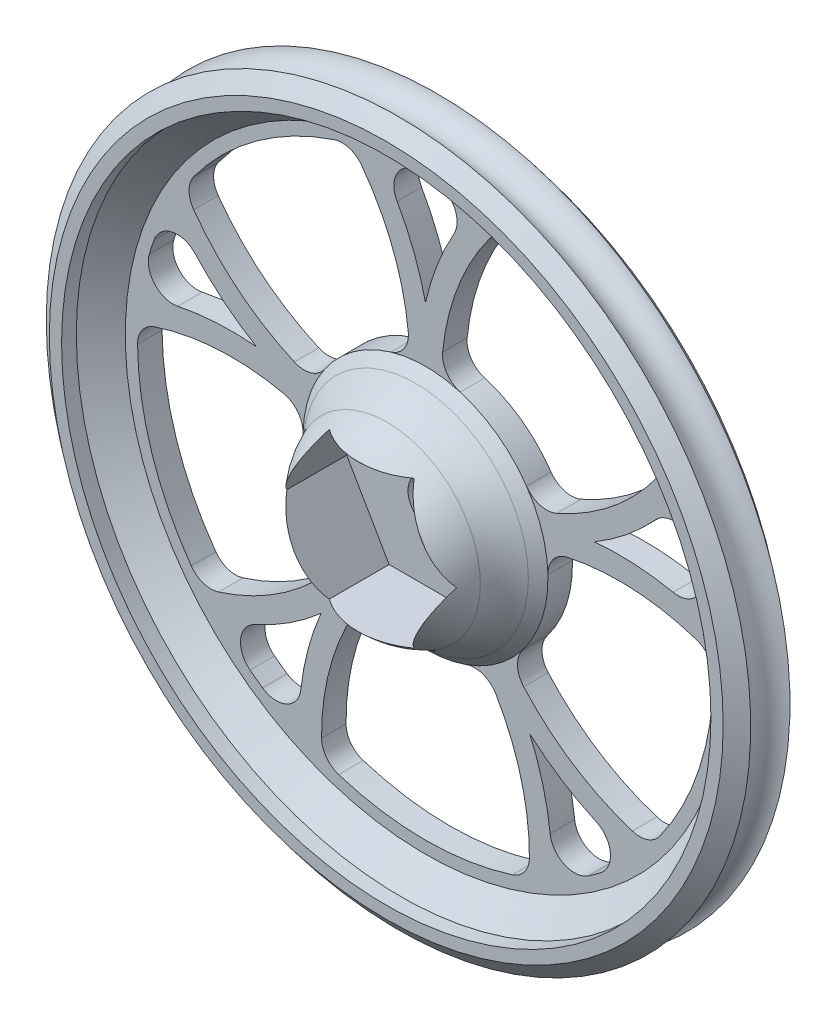
SolidWorks part; units mm, degrees
ref_plane "Front Plane" through (0, 0, 0) normal (0, 0, 1) x (1, 0, 0)
ref_plane "Top Plane" through (0, 0, 0) normal (0, 1, 0) x (1, 0, 0)
ref_plane "Right Plane" through (0, 0, 0) normal (1, 0, 0) x (0, 0, -1)
sketch "Sketch1" plane through (0, 0, 0) normal (1, 0, 0) x (0, 0, -1)
  line L0 (1, 1.925) -> (-1, 1.925)
  line L1 (-1, 8) -> (-1, 26.5)
  line L2 (-1, 26.5) -> (-4.2016, 26.5)
  line L3 (-4.2016, 26.5) -> (-4.2016, 27.5)
  line L4 (-4.2016, 27.5) -> (-3.2016, 28.75)
  line L5 (-3.2016, 28.75) -> (0, 28.75) construction
  line L6 (0, 28.75) -> (1, 27.5)
  line L7 (1, 27.5) -> (1, 26.5)
  line L8 (0, 1.925) -> (0, 26.5) construction
  line L9 (1, 26.5) -> (1, 1.925)
  line L10 (0, 0) -> (0, 1.925) construction
  line L11 (0, 0) -> (-35.662, 0) construction
  line L12 (-4.2016, 27.5) -> (1, 27.5) construction
  line L13 (-1, 26.5) -> (1, 26.5) construction
  line L14 (-1, 1.925) -> (-6.5, 1.925)
  line L15 (-6.5, 1.925) -> (-6.5, 8)
  line L16 (-6.5, 8) -> (-1, 8)
  arc A0 (-3.2016, 28.75) -> (0, 28.75) centre (-1.6008, 29.15) ccw
  dimension "D3" = 1.65
  dimension "D1" = 27.5
  dimension "D2" = 2
  dimension "D4" = 1
  dimension "D5" = 1
  dimension "D6" = 1.925
  dimension "D7" = 1.25
  dimension "D8" = 8
  dimension "D9" = 7.5
revolve "Revolve1" add sketch "Sketch1" angle 360 about L11
chamfer "Chamfer1" distance 2 angle 45 3 edges at (-8, 0, 6.5) (-8, 0, 1) (-26.5, 0, 1)
sketch "Sketch2" plane through (0, 0, 6.5) normal (0, 0, 1) x (1, 0, 0)
  line L0 (3.4641, 6) -> (-3.4641, 6)
  line L1 (-3.4641, 6) -> (-6.9282, 0)
  line L2 (-6.9282, 0) -> (-3.4641, -6)
  line L3 (-3.4641, -6) -> (3.4641, -6)
  line L4 (3.4641, -6) -> (6.9282, 0)
  line L5 (6.9282, 0) -> (3.4641, 6)
  circle A0 centre (0, 0) radius 6.9282 construction
  point P8 (4.4333, -1.0405)
  point P10 (0, 0)
  point P11 (0, 0)
  point P12 (0, 0)
  point P13 (1.925, -2.4583)
  point P14 (0, 0)
  point P15 (0, 0)
  dimension "D1" = 12
extrude "Cut-Extrude1" cut sketch "Sketch2" against normal blind 6
sketch "Sketch4" plane through (0, 0, 1) normal (0, 0, 1) x (1, 0, 0)
  line L0 (0, 0) -> (0, 24.5) construction
  line L1 (0, 0) -> (-23.3009, 7.5709) construction
  line L2 (-19.7088, 12.799) -> (-6.0822, 22.6993) construction
  line L3 (0, 0) -> (-12.8955, 17.7491) construction
  line L4 (0, 0) -> (-1.3053, 9.9144) construction
  line L5 (0, 0) -> (-6.0822, 22.6993) construction
  line L6 (-9.0259, 4.3051) -> (0, 0) construction
  line L7 (0, 0) -> (-19.7088, 12.799) construction
  line L8 (0, 0) -> (-4.0807, 23.143) construction
  circle A0 centre (0, 0) radius 24.5 construction
  arc A1 (-9.0259, 4.3051) -> (-1.3053, 9.9144) centre (0, 0) cw
  arc A2 (-19.7088, 12.799) -> (-6.0822, 22.6993) centre (0, 0) cw
  circle A3 centre (0, 0) radius 10 construction
  arc A4 (-19.7088, 12.799) -> (-9.0259, 4.3051) centre (-2.6672, 23.2674) ccw
  arc A5 (-1.3053, 9.9144) -> (-6.0822, 22.6993) centre (-21.3044, 9.7267) ccw
  arc A6 (-4.0807, 23.143) -> (4.0807, 23.143) centre (0, 0) cw
  arc A7 (4.0807, 23.143) -> (0, 14.4989) centre (21.3044, 9.7267) ccw
  arc A8 (0, 14.4989) -> (-4.0807, 23.143) centre (-21.3044, 9.7267) ccw
  point P8 (0, 23.5)
  point P23 (4.4157, 23.143)
  dimension "D2" = 23.5
  dimension "D7" = 20
  dimension "D1" = 72
  dimension "D3" = 36
  dimension "D4" = 7.5
  dimension "D5" = 15
  dimension "D6" = 7.5
  dimension "D8" = 5
extrude "Cut-Extrude2" cut sketch "Sketch4" against normal through all both and the other way through all
fillet "Fillet2" radius 2 6 edges at (-1.3053, 9.9144, 0) (-9.0259, 4.3051, 0) (-19.7088, 12.799, 0) (-6.0822, 22.6993, 0) (4.0807, 23.143, 0) (-4.0807, 23.143, 0)
pattern_circular "CirPattern1" count 5 over 360 about axis through (0, 0, 0) along (0, 0, 1) of "Cut-Extrude2", "Fillet2" reverse direction yes
fillet "Fillet3" radius 7.5 1 edges at (8, 0, 4.5)
fillet "Fillet4" radius 7.5 1 edges at (8, 0, 3)
